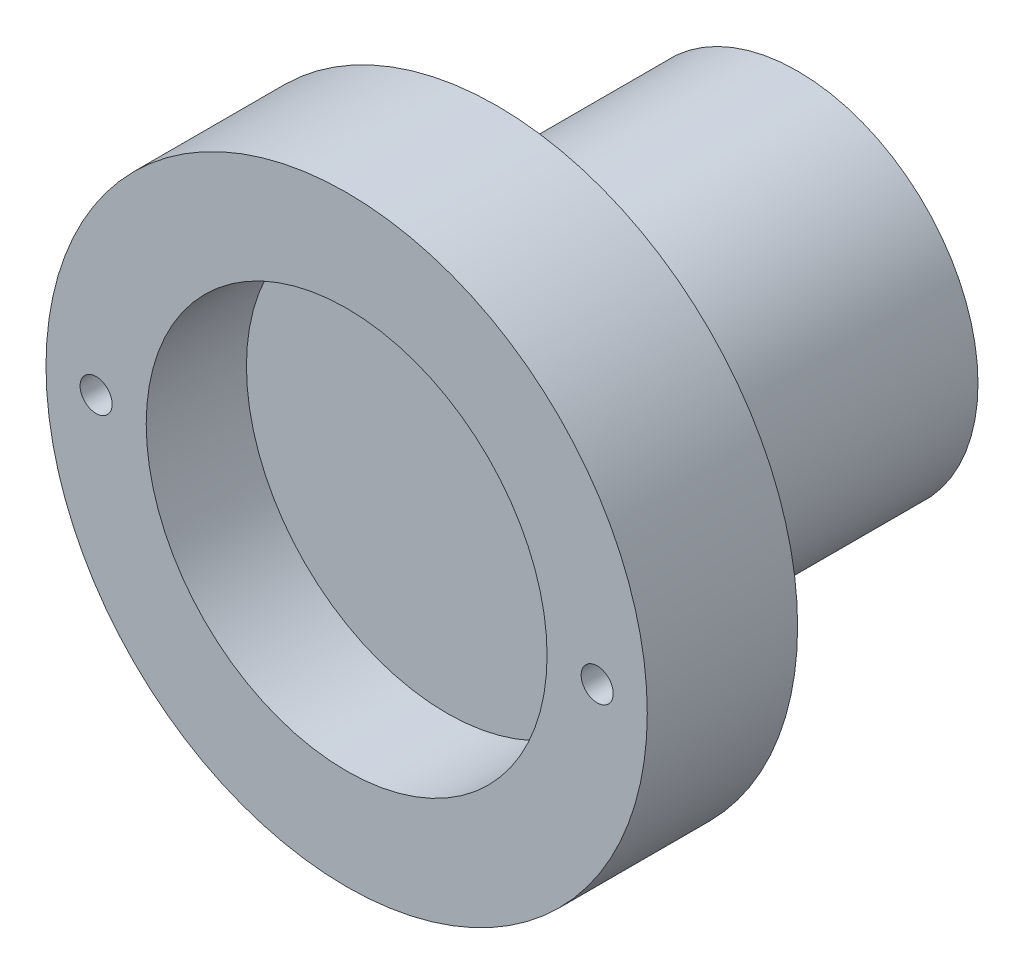
SolidWorks part; units mm, degrees
ref_plane "Front Plane" through (0, 0, 0) normal (0, 0, 1) x (1, 0, 0)
ref_plane "Top Plane" through (0, 0, 0) normal (0, 1, 0) x (1, 0, 0)
ref_plane "Right Plane" through (0, 0, 0) normal (1, 0, 0) x (0, 0, -1)
sketch "Sketch1" plane through (0, 0, 0) normal (0, 0, 1) x (1, 0, 0)
  line L0 (-25, 0) -> (0, 0) construction
  line L1 (0, 0) -> (25, 0) construction
  circle A0 centre (0, 0) radius 30
  circle A1 centre (-25, 0) radius 1.6
  circle A2 centre (25, 0) radius 1.6
  dimension "D1" = 25
extrude "Boss-Extrude1" add sketch "Sketch1" along normal blind 15
sketch "Sketch2" plane through (0, 0, 15) normal (0, 0, 1) x (1, 0, 0)
  circle A0 centre (0, 0) radius 20
extrude "Cut-Extrude1" cut sketch "Sketch2" against normal blind 10
sketch "Sketch3" plane through (0, 0, 0) normal (0, 0, -1) x (-1, 0, 0)
  circle A0 centre (0, 0) radius 18
extrude "Boss-Extrude2" add sketch "Sketch3" along normal blind 30
sketch "Sketch4" plane through (0, 0, -30) normal (0, 0, -1) x (-1, 0, 0)
  circle A0 centre (0, 0) radius 16
extrude "Cut-Extrude2" cut sketch "Sketch4" against normal blind 25
